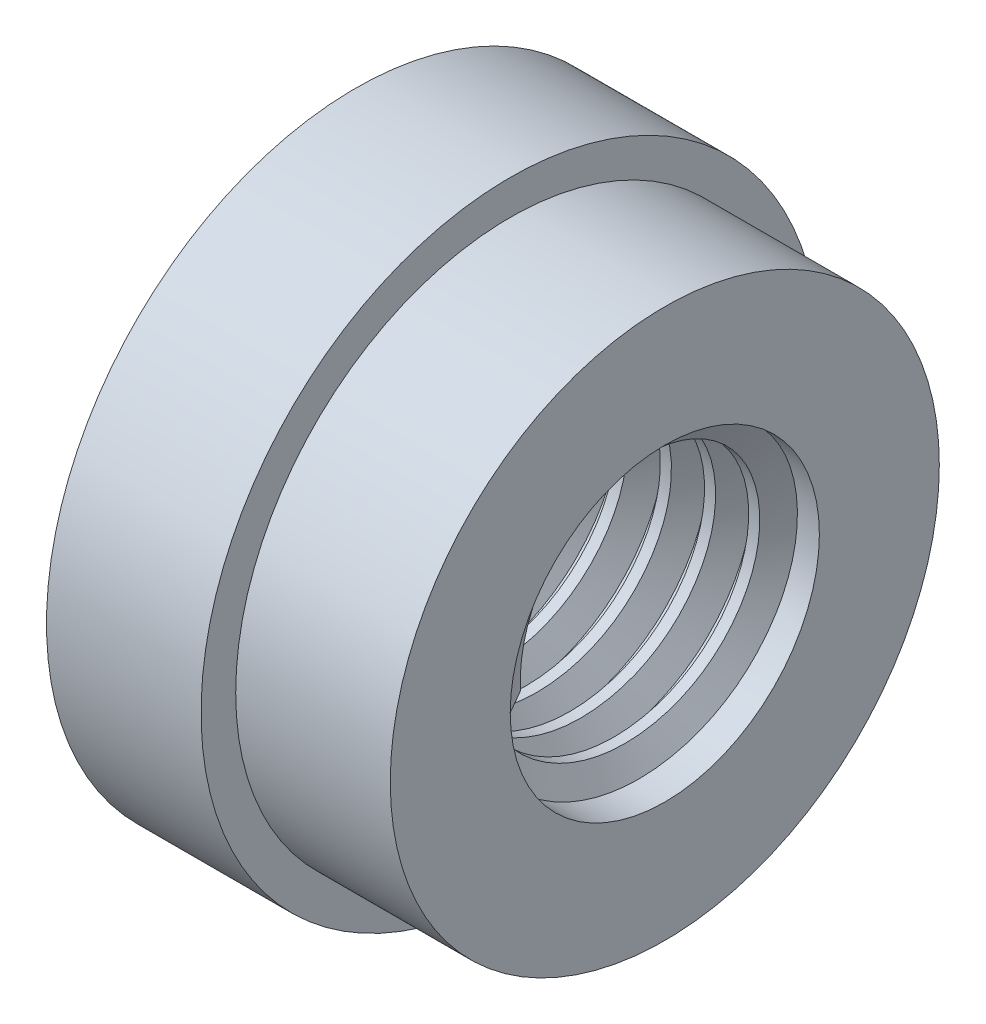
SolidWorks part; units mm, degrees
ref_plane "Front Plane" through (0, 0, 0) normal (0, 0, 1) x (1, 0, 0)
ref_plane "Top Plane" through (0, 0, 0) normal (0, 1, 0) x (1, 0, 0)
ref_plane "Right Plane" through (0, 0, 0) normal (1, 0, 0) x (0, 0, -1)
sketch "Sketch1" plane through (0, 0, 0) normal (1, 0, 0) x (0, 0, -1)
  circle A0 centre (0, 0) radius 6.35
  dimension "D1" = 12.7
extrude "Boss-Extrude1" add sketch "Sketch1" along normal blind 3.175
sketch "Sketch2" plane through (3.175, 0, 0) normal (1, 0, 0) x (0, 0, -1)
  circle A0 centre (0, 0) radius 5.6388
  dimension "D1" = 11.2776
extrude "Boss-Extrude2" add sketch "Sketch2" along normal blind 3.175
sketch "Sketch3" plane through (6.35, 0, 0) normal (1, 0, 0) x (0, 0, -1)
  circle A0 centre (0, 0) radius 3.175
  dimension "D1" = 6.35
extrude "Cut-Extrude1" cut sketch "Sketch3" against normal through all
thread "Thread2" pitch 0.9071 method extrude trim with end face yes profile "Thread Profile3" start angle 0, offset 0, length 0, pitch 0.9071, diameter 6.35
ref_plane "Plane3" through (6.35, 0, 3.175) normal (0, -1, 0) x (0, 0, 1)
sketch "Thread Profile3" plane through (6.35, 0, 3.175) normal (0, -1, 0) x (0, 0, 1)
  line L0 (0, 0) -> (0, 0.9071) construction
  line L11 (0, 0) -> (0, 0.7937)
  line L12 (0, 0.7937) -> (-0.491, 0.5103)
  line L13 (-0.491, 0.5103) -> (-0.491, 0.2835)
  line L15 (-0.491, 0.2835) -> (0, 0)
  line L17 (-0.491, 0.3969) -> (0, 0.3969) construction
  point P2 (0, 0)
  dimension "Pitch" = 0.9071
  dimension "Profile_Angle" = 60
  dimension "Profile_Land" = 0.2268
  dimension "Profile_Height" = 0.491
